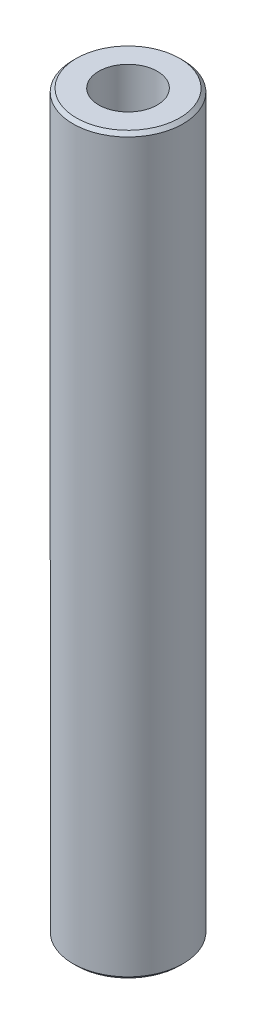
SolidWorks part; units mm, degrees
ref_plane "Front Plane" through (0, 0, 0) normal (0, 0, 1) x (1, 0, 0)
ref_plane "Top Plane" through (0, 0, 0) normal (0, 1, 0) x (1, 0, 0)
ref_plane "Right Plane" through (0, 0, 0) normal (1, 0, 0) x (0, 0, -1)
sketch "Sketch1" plane through (0, 0, 0) normal (0, 1, 0) x (1, 0, 0)
  circle A0 centre (0, 0) radius 45
  dimension "SHAFT_OD" = 90
extrude "Boss-Extrude1" add sketch "Sketch1" along normal blind 600
sketch "Sketch2" plane through (0, 0, 0) normal (0, 1, 0) x (1, 0, 0)
  circle A0 centre (0, 0) radius 23.9099
  dimension "BORE_D" = 47.8198
extrude "Cut-Extrude1" cut sketch "Sketch2" along normal through all
chamfer "Chamfer1" distance 2.7863 angle 45 2 edges at (0, 600, 45) (0, 0, 45)
